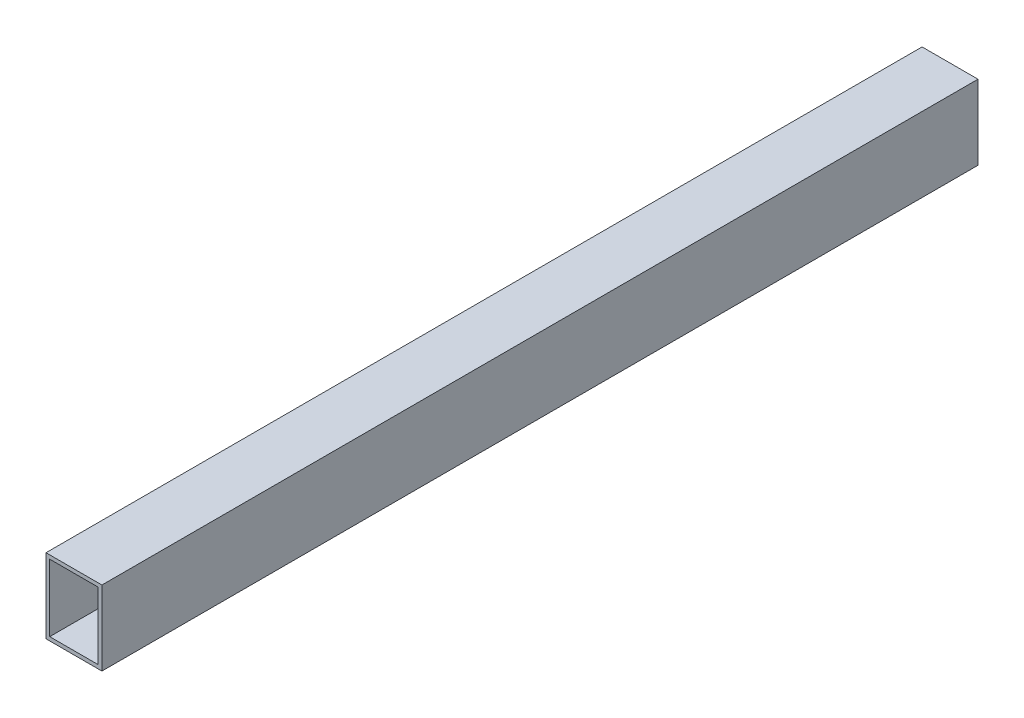
SolidWorks part; units mm, degrees
material "1060 合金"
ref_plane "前视基准面" through (0, 0, 0) normal (0, 0, 1) x (1, 0, 0)
ref_plane "上视基准面" through (0, 0, 0) normal (0, 1, 0) x (1, 0, 0)
ref_plane "右视基准面" through (0, 0, 0) normal (1, 0, 0) x (0, 0, -1)
other "Configuration Table"
sketch "草图1" plane through (0, 0, 0) normal (0, 0, 1) x (1, 0, 0)
  line L1 (0, 0) -> (15, 0)
  line L2 (0, 0) -> (0, -20)
  line L3 (0, -20) -> (15, -20)
  line L4 (15, 0) -> (15, -20)
  dimension "D1" = 20
  dimension "D2" = 15
extrude "拉伸-薄壁1" add sketch "草图1" along normal blind 235 thin thin type one direction reverse wall 1
sketch "草图2" plane through (0, -20, 0) normal (0, -1, 0) x (1, 0, 0)
  circle A1 centre (7.5, 825) radius 2.6
  circle A2 centre (7.5, 825) radius 2.6
  dimension "D1" = 0
extrude "切除-拉伸1" [suppressed] cut sketch "草图2" against normal up to next
